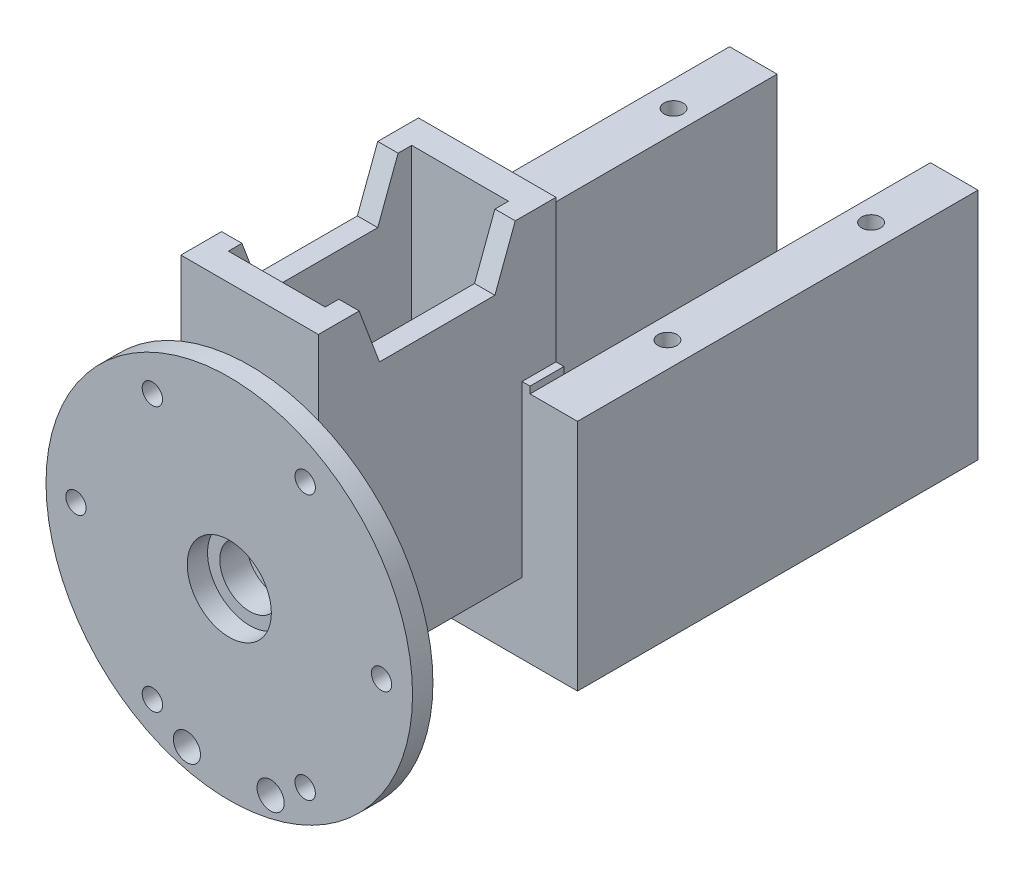
SolidWorks part; units mm, degrees
ref_plane "前视基准面" through (0, 0, 0) normal (0, 0, 1) x (1, 0, 0)
ref_plane "上视基准面" through (0, 0, 0) normal (0, 1, 0) x (1, 0, 0)
ref_plane "右视基准面" through (0, 0, 0) normal (1, 0, 0) x (0, 0, -1)
sketch "草图1" plane through (0, 0, 0) normal (0, 0, 1) x (1, 0, 0)
  line L0 (0, 0) -> (0, -7)
  line L1 (0, -7) -> (7.13, -7)
  line L2 (0, -7) -> (-7.13, -7)
  line L3 (-7.13, -4) -> (-7.13, 36)
  line L6 (-7.13, -4) -> (-4.13, -7)
  line L7 (7.13, -4) -> (4.13, -7)
  line L8 (7.13, -4) -> (7.13, 36)
  line L9 (7.13, 36) -> (-7.13, 36)
  line L10 (-7.13, -7) -> (-7.13, -10)
  line L11 (-7.13, -10) -> (-10.13, -10)
  line L12 (7.13, -7) -> (7.13, -10)
  line L13 (7.13, -10) -> (10.13, -10)
  line L14 (-7.13, 36) -> (-10.13, 36)
  line L15 (7.13, 36) -> (10.13, 36)
  line L16 (-10.13, -10) -> (-10.13, 36)
  line L17 (10.13, 36) -> (10.13, -10)
  line L18 (-7.13, -10) -> (7.13, -10)
  circle A0 centre (0, 0) radius 4.4
extrude "凸台-拉伸1" add sketch "草图1" along normal blind 13.5 contours L16 L11 L10 L2 L6 L3 L14 | L10 L18 L12 L1 L2 | L17 L15 L8 L7 L1 L12 L13 region at (0, -8.5, 0) region at (8.5511, 12.4, 0) region at (-8.5511, 12.4, 0)
extrude "凸台-拉伸2" add sketch "草图1<3>" against normal blind 4 contours A0 L1 L7 L8 L9 L3 L6 L2 | L10 L18 L12 L1 L2 | L17 L15 L8 L7 L1 L12 L13 | L16 L11 L10 L2 L6 L3 L14 region at (0, 16.4626, 0) region at (0, -8.5, 0) region at (8.5511, 12.4, 0) region at (-8.5511, 12.4, 0)
sketch "草图1<3>" plane through (0, 0, 0) normal (0, 0, 1) x (1, 0, 0) same geometry as "草图1"
mirror "镜向1" about plane through (0, 0, 13.5) normal (0, 0, 1) of "凸台-拉伸1", "凸台-拉伸2"
sketch "草图2" plane through (-10.13, 0, 0) normal (-1, 0, 0) x (0, 0, 1)
  line L1 (31, 36) -> (-4, 36) construction
  line L9 (2, 36) -> (5, 28)
  line L10 (5, 28) -> (22, 28)
  line L11 (22, 28) -> (25, 36)
  line L12 (25, 36) -> (2, 36)
extrude "切除-拉伸1" cut sketch "草图2" against normal blind 40
sketch "草图3" plane through (-10.13, 0, 0) normal (-1, 0, 0) x (0, 0, 1)
  line L0 (5, 12) -> (17.2973, 12)
  line L2 (5, 9) -> (5, 12)
  line L4 (17.2973, 9) -> (5, 9)
  line L6 (17.2973, 12) -> (17.2973, 16)
  line L7 (17.2973, 9) -> (17.2973, 5)
  line L8 (17.2973, 5) -> (22, 10.5)
  line L9 (22, 10.5) -> (17.2973, 16)
extrude "切除-拉伸2" cut sketch "草图3" against normal blind 0.5
sketch "草图4" plane through (0, 0, 31) normal (0, 0, 1) x (1, 0, 0)
  circle A0 centre (0, 0) radius 6.2
  circle A1 centre (0, 0) radius 27
  circle A2 centre (6.0883, -23.3094) radius 2
  circle A3 centre (22.4349, -0.2829) radius 1.5
  circle A4 centre (11.1797, 19.2117) radius 1.5
  circle A5 centre (-11.3307, 19.2117) radius 1.5
  circle A6 centre (-22.5858, -0.2829) radius 1.5
  circle A7 centre (-11.3307, -19.7774) radius 1.5
  circle A8 centre (11.1797, -19.7774) radius 1.5
  circle A9 centre (-6.2393, -23.3094) radius 2
  point P0 (0, 0)
extrude "凸台-拉伸3" add sketch "草图4" along normal blind 3
sketch "草图8" plane through (-10.13, 0, 0.9916) normal (-1, 0, 0) x (0, 0, 1)
  line L0 (30, 21.3804) -> (27.7348, 21.3804)
  line L1 (27.7348, 21.3804) -> (27.7348, 17.1228)
  line L2 (27.7348, 17.1228) -> (30, 17.1228)
  line L3 (30, 17.1228) -> (30, 21.3804)
  point P3 (30, 20.0643)
extrude "切除-拉伸4" cut sketch "草图8" against normal blind 30 contours L0 L1 L2 L3
sketch "草图11" plane through (0, 0, -4) normal (0, 0, -1) x (-1, 0, 0)
  line L0 (0, 0) -> (11.3, 0)
  line L1 (11.3, 0) -> (11.3, -15)
  line L2 (11.3, -15) -> (-11.3, -15)
  line L3 (-11.3, -15) -> (-11.3, 15)
  line L4 (-11.3, 15) -> (11.3, 15)
  line L5 (11.3, 15) -> (11.3, 0)
  line L6 (-18.3, 14) -> (-18.3, -17.417)
  line L7 (-18.3, -17.417) -> (-18.3, -20.417)
  line L8 (-18.3, 14) -> (-11.3, 14)
  line L9 (11.3, 14) -> (18.3, 14)
  line L10 (18.3, 14) -> (18.3, -20.417)
  line L11 (18.3, -20.417) -> (-18.3, -20.417)
  line L12 (-10.13, 15) -> (-10.13, -10)
  line L13 (-10.13, 36) -> (-10.13, -10) construction
  line L14 (-10.13, -10) -> (10.13, -10) construction
  line L15 (-10.13, -10) -> (10.13, -10)
  line L16 (10.13, -10) -> (10.13, 15)
  line L17 (10.13, -10) -> (10.13, 36) construction
  line M11 (-10.13, -10) -> (10.13, -10)
  line M12 (10.13, -10) -> (10.13, 36)
  line M14 (-10.13, 36) -> (-10.13, -10)
extrude "凸台-拉伸11" add sketch "草图11" against normal blind 5 contours L4 L3 L2 L1 L0 M12 M11 M14 | L5 L4 L0 M12 region at (-10.715, 7.5, -4) region at (-10.715, -0.3756, -4)
extrude "凸台-拉伸12" add sketch "草图11<3>" against normal blind 5 contours L11 L10 L9 L5 L1 L2 L3 L8 L6 L7 region at (-11.8024, 7, -4)
sketch "草图11<3>" plane through (0, 0, -4) normal (0, 0, -1) x (-1, 0, 0) same geometry as "草图11"
extrude "凸台-拉伸13" add sketch "草图11<4>" along normal blind 54 contours L11 L10 L9 L5 L1 L2 L3 L8 L6 L7 region at (-11.8024, 7, -4)
sketch "草图11<4>" plane through (0, 0, -4) normal (0, 0, -1) x (-1, 0, 0) same geometry as "草图11"
sketch "草图12" plane through (-18.3, 0, 0) normal (-1, 0, 0) x (0, 0, 1)
  line L0 (-4, 14) -> (-4, 11)
sketch "草图13" plane through (0, 14, 0) normal (0, 1, 0) x (1, 0, 0)
  line L0 (-11.3, -1) -> (-14.55, -1)
  line L1 (-11.3, -1) -> (-18.3, -1) construction
  circle A0 centre (-14.55, 16) radius 1.4
  circle A1 centre (-14.55, 46) radius 1.4
  point P7 (0, 0)
extrude "切除-拉伸5" cut sketch "草图13" against normal blind 5 contours A0 | A1
sketch "草图14" plane through (0, 14, 0) normal (0, 1, 0) x (1, 0, 0)
  line L0 (11.3, 4) -> (14.55, 4)
  circle A0 centre (14.55, 16) radius 1.4
  circle A1 centre (14.55, 46) radius 1.4
extrude "切除-拉伸6" cut sketch "草图14" against normal blind 5 contours A0 | A1 region at (14.55, 14, -16)
